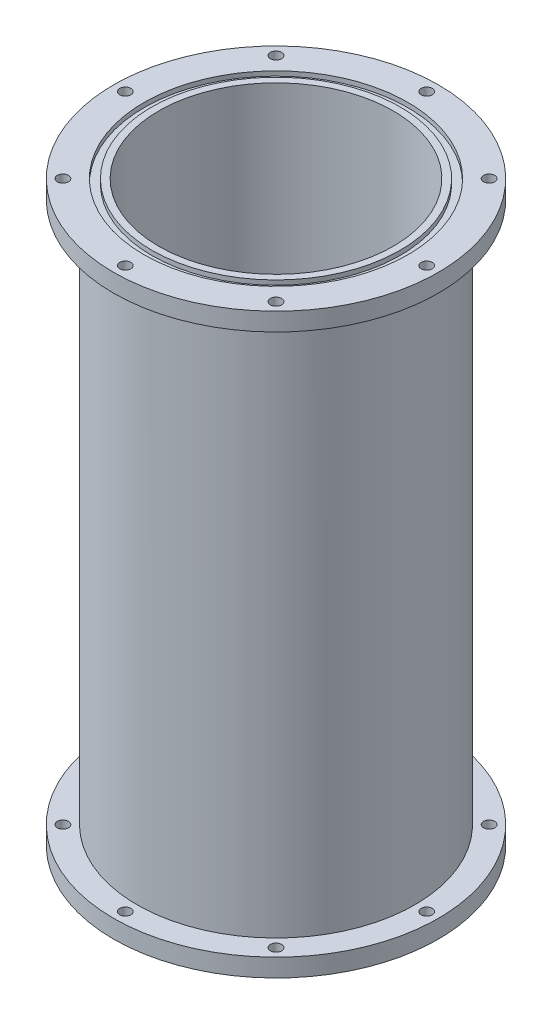
SolidWorks part; units mm, degrees
material "6061-T6 (SS)"
ref_plane "Front Plane" through (0, 0, 0) normal (0, 0, 1) x (1, 0, 0)
ref_plane "Top Plane" through (0, 0, 0) normal (0, 1, 0) x (1, 0, 0)
ref_plane "Right Plane" through (0, 0, 0) normal (1, 0, 0) x (0, 0, -1)
sketch "Sketch3" plane through (0, 0, 0) normal (0, 1, 0) x (1, 0, 0)
  circle A0 centre (0, 0) radius 32.5
  circle A1 centre (0, 0) radius 38.5
extrude "Boss-Extrude3" add sketch "Sketch3" along normal blind 160
sketch "Sketch5" plane through (0, 0, 0) normal (0, -1, 0) x (1, 0, 0)
  circle A0 centre (0, 0) radius 45
  circle A1 centre (0, 0) radius 32.5
  circle A2 centre (0, 0) radius 35.6743
  circle A3 centre (0, 0) radius 36.7411
  circle A4 centre (0, 0) radius 34.6075
  circle M1 centre (0, 0) radius 38.5
extrude "Cut-Extrude1" cut sketch "Sketch5" against normal blind 1.4224 contours A3 A2 | A2 A4 region at (-34.6653, 0, 0) region at (-35.7019, 0, 0)
extrude "Boss-Extrude5" add sketch "Sketch5<4>" against normal blind 5 contours A0 M1 region at (-43.7272, 0, 0)
sketch "Sketch5<4>" plane through (0, 0, 0) normal (0, -1, 0) x (1, 0, 0) same geometry as "Sketch5"
sketch "Sketch7" plane through (0, 5, 0) normal (0, 1, 0) x (1, 0, 0)
  circle A3 centre (0, 41.75) radius 1.55
  circle A4 centre (29.5217, 29.5217) radius 1.55
  circle A5 centre (41.75, 0) radius 1.55
  circle A6 centre (29.5217, -29.5217) radius 1.55
  circle A7 centre (0, -41.75) radius 1.55
  circle A8 centre (-29.5217, -29.5217) radius 1.55
  circle A9 centre (-41.75, 0) radius 1.55
  circle A10 centre (-29.5217, 29.5217) radius 1.55
  point P20 (0, 0)
  dimension "D1" = 8
extrude "Cut-Extrude2" cut sketch "Sketch7" against normal blind 5
sketch "Sketch9" plane through (0, 160, 0) normal (0, 1, 0) x (1, 0, 0)
  circle A0 centre (0, 0) radius 32.5
  circle A1 centre (0, 0) radius 38.5
extrude "Cut-Extrude3" cut sketch "Sketch9" against normal blind 80
mirror "Mirror7" about plane through (0, 80, 0) normal (0, 1, 0) of "Boss-Extrude3", "Cut-Extrude1", "Boss-Extrude5", "Cut-Extrude2"
extrude "Cut-Extrude6" cut sketch "Sketch5<7>" against normal blind 1.4224 contours A3 A2 | A2 A4 region at (-34.6653, 0, 0) region at (-35.7019, 0, 0)
sketch "Sketch5<7>" plane through (0, 0, 0) normal (0, -1, 0) x (1, 0, 0) same geometry as "Sketch5"
sketch "Sketch10" plane through (0, 160, 0) normal (0, 1, 0) x (1, 0, 0)
  circle A0 centre (0, 0) radius 34.6075
  circle A1 centre (0, 0) radius 36.7411
extrude "Boss-Extrude6" add sketch "Sketch10" against normal up to surface (160 mm away) up to face at (0, 0, -36.7411)
sketch "Sketch11" plane through (0, 160, 0) normal (0, 1, 0) x (1, 0, 0)
  circle A0 centre (0, 0) radius 36.5633
  circle A1 centre (0, 0) radius 34.4043
extrude "Cut-Extrude7" cut sketch "Sketch11" against normal blind 1.27
sketch "Sketch12" plane through (0, 0, 0) normal (0, -1, 0) x (1, 0, 0)
  circle A0 centre (0, 0) radius 36.5633
  circle A1 centre (0, 0) radius 34.4043
extrude "Cut-Extrude8" cut sketch "Sketch12" against normal blind 1.27
